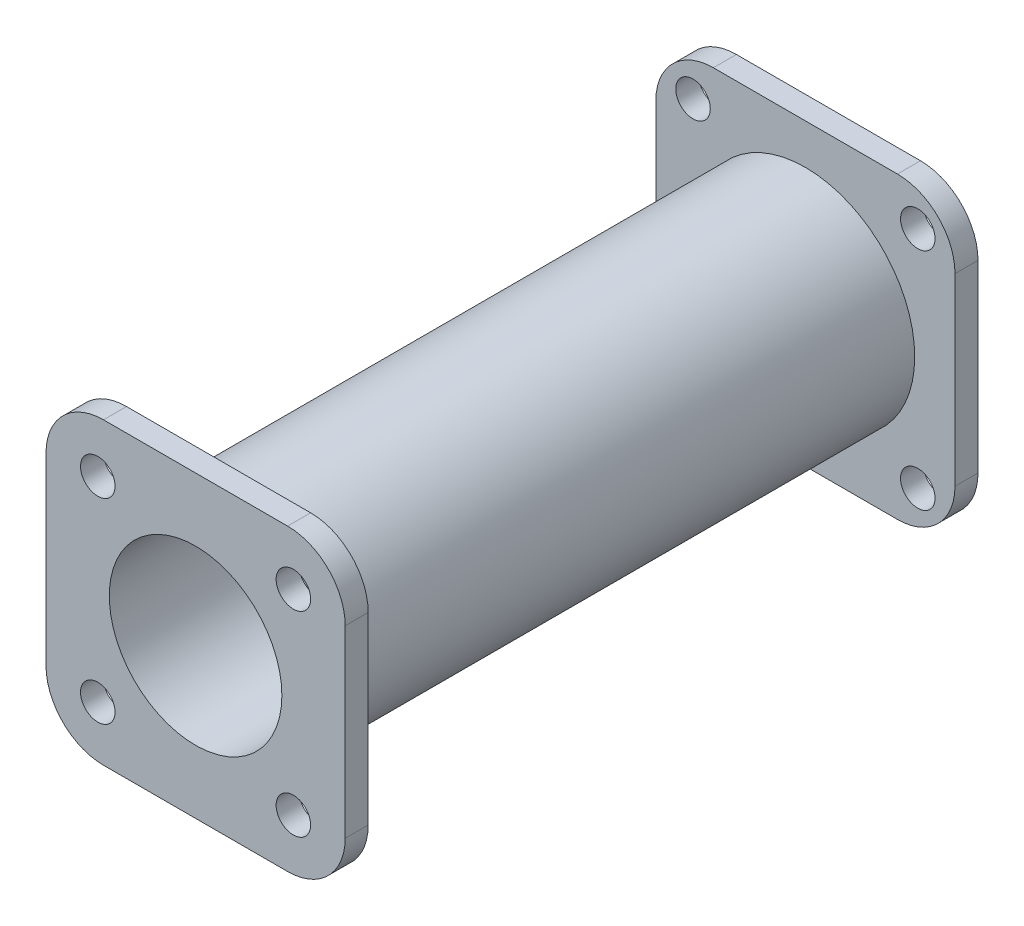
SolidWorks part; units mm, degrees
ref_plane "前视基准面" through (0, 0, 0) normal (0, 0, 1) x (1, 0, 0)
ref_plane "上视基准面" through (0, 0, 0) normal (0, 1, 0) x (1, 0, 0)
ref_plane "右视基准面" through (0, 0, 0) normal (1, 0, 0) x (0, 0, -1)
other "Configuration Table"
sketch "草图1" plane through (0, 0, 0) normal (0, 0, 1) x (1, 0, 0)
  line L0 (0, 0) -> (0, -50000) construction
  line L1 (-8, 13) -> (8, 13)
  line L2 (-13, 8) -> (-13, -8)
  line L3 (-8, -13) -> (8, -13)
  line L4 (13, 8) -> (13, -8)
  line L5 (-13, 13) -> (13, -13) construction
  line L6 (-13, -13) -> (13, 13) construction
  line L7 (0, 0) -> (50000, 0) construction
  circle A0 centre (0, 0) radius 9.5
  circle A1 centre (0, 0) radius 7.5
  arc A2 (-13, 8) -> (-8, 13) centre (-8, 8) cw
  arc A3 (8, 13) -> (13, 8) centre (8, 8) cw
  arc A4 (13, -8) -> (8, -13) centre (8, -8) cw
  arc A5 (-13, -8) -> (-8, -13) centre (-8, -8) ccw
  circle A6 centre (-9.7678, 9.7678) radius 1.5
  circle A7 centre (-9.7678, -9.7678) radius 1.5
  circle A8 centre (9.7678, 9.7678) radius 1.5
  circle A9 centre (9.7678, -9.7678) radius 1.5
  point P0 (0, 0)
  point P29 (-11.5355, 11.5355)
  point P32 (0, -13)
  dimension "D3" = 5
  dimension "D4" = 19
  dimension "D5" = 15
  dimension "D6" = 3
  dimension "D1" = 26
  dimension "D2" = 26
  dimension "D7" = 2.5
extrude "凸台-拉伸1" add sketch "草图1" along normal blind 2 contours L2 A5 L3 A4 L4 A3 L1 A2 A0 region at (0, 12.6323, 0)
extrude "凸台-拉伸2" add sketch "草图1<6>" along normal blind 55 contours A0 A1 region at (-9.2313, 0, 0)
sketch "草图1<6>" plane through (0, 0, 0) normal (0, 0, 1) x (1, 0, 0) same geometry as "草图1"
sketch "草图5" plane through (0, 0, 55) normal (0, 0, 1) x (1, 0, 0)
  line L0 (0, 0) -> (0, -50000) construction
  line L1 (-8, 13) -> (8, 13)
  line L2 (-13, 8) -> (-13, -8)
  line L3 (-8, -13) -> (8, -13)
  line L4 (13, 8) -> (13, -8)
  line L5 (-13, 13) -> (13, -13) construction
  line L6 (-13, -13) -> (13, 13) construction
  line L7 (0, 0) -> (50000, 0) construction
  arc A2 (-8, -13) -> (-13, -8) centre (-8, -8) cw
  arc A3 (8, -13) -> (13, -8) centre (8, -8) ccw
  arc A4 (13, 8) -> (8, 13) centre (8, 8) ccw
  arc A5 (-8, 13) -> (-13, 8) centre (-8, 8) ccw
  circle A10 centre (-8.5, -8.5) radius 1.5
  circle A11 centre (8.5, -8.5) radius 1.5
  circle A14 centre (8.5, 8.5) radius 1.5
  circle A15 centre (-8.5, 8.5) radius 1.5
  circle A16 centre (0, 0) radius 7.5
  circle A17 centre (0, 0) radius 9.5
  point P0 (0, 0)
  circle M6 centre (0, 0) radius 9.5
  dimension "D3" = 5
  dimension "D1" = 26
  dimension "D2" = 26
  dimension "D5" = 17
  dimension "D6" = 8.5
extrude "凸台-拉伸3" add sketch "草图5" against normal blind 2 contours L1 A5 L2 A2 L3 A3 L4 A4 M6 region at (0, 12.6323, 55)
